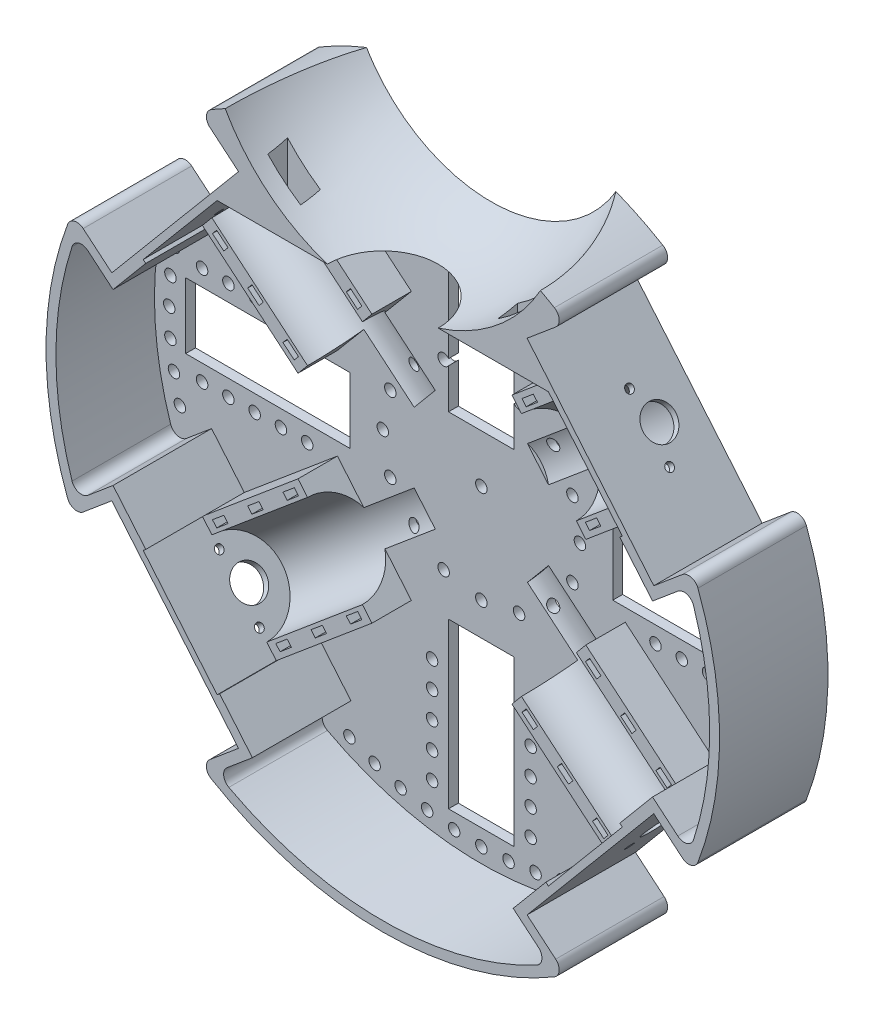
SolidWorks part; units mm, degrees
ref_plane "Front Plane" through (0, 0, 0) normal (0, 0, 1) x (1, 0, 0)
ref_plane "Top Plane" through (0, 0, 0) normal (0, 1, 0) x (1, 0, 0)
ref_plane "Right Plane" through (0, 0, 0) normal (1, 0, 0) x (0, 0, -1)
sketch "Sketch1" plane through (0, 0, 0) normal (0, 0, 1) x (1, 0, 0)
  circle A0 centre (0, 0) radius 102.5
  dimension "D1" = 205
extrude "Boss-Extrude1" add sketch "Sketch1" along normal blind 3
sketch "Sketch2" plane through (0, 0, 3) normal (0, 0, 1) x (1, 0, 0)
  line L0 (78.5196, 65.8857) -> (0, 0) construction
  line L1 (0, 0) -> (102.5, 0) construction
  line L2 (74.5568, 101.7228) -> (113.1241, 55.7601)
  line L3 (74.5568, 101.7228) -> (43.915, 76.0113)
  line L4 (113.1241, 55.7601) -> (82.4823, 30.0486)
  line L5 (43.915, 76.0113) -> (82.4823, 30.0486)
  line L6 (74.5568, 101.7228) -> (82.4823, 30.0486) construction
  line L7 (113.1241, 55.7601) -> (43.915, 76.0113) construction
  circle A0 centre (0, 0) radius 102.5 construction
  dimension "D1" = 40
  dimension "D2" = 60
  dimension "D3" = 40
extrude "Cut-Extrude1" cut sketch "Sketch2" against normal blind 3
sketch "Sketch3" plane through (0, 0, 3) normal (0, 0, 1) x (1, 0, 0)
  line L0 (51.9499, 66.4358) -> (74.4474, 39.6242)
  line L1 (51.9499, 66.4358) -> (21.3081, 40.7243)
  line L2 (74.4474, 39.6242) -> (43.8057, 13.9127)
  line L3 (21.3081, 40.7243) -> (43.8057, 13.9127)
  line L4 (43.915, 76.0113) -> (82.4823, 30.0486) construction
  point P6 (63.1987, 53.03)
  dimension "D1" = 35
  dimension "D2" = 40
extrude "Boss-Extrude2" add sketch "Sketch3" along normal blind 12
sketch "Sketch4" plane through (63.1987, 53.03, 0) normal (0.766, 0.6428, 0) x (0, 0, -1)
  line L0 (-15, -17.5) -> (-15, 17.5) construction
  circle A0 centre (-15, 0) radius 13
  dimension "D1" = 26
extrude "Cut-Extrude2" cut sketch "Sketch4" against normal blind 60
sketch "Sketch5" plane through (0, 0, 15) normal (0, 0, 1) x (1, 0, 0)
  line L0 (26.7453, 42.0231) -> (48.1945, 60.0211) construction
  line L1 (26.7453, 42.0231) -> (46.0289, 19.0417) construction
  line L2 (48.1945, 60.0211) -> (67.4782, 37.0398) construction
  line L3 (46.0289, 19.0417) -> (67.4782, 37.0398) construction
  line L4 (51.9499, 66.4358) -> (21.3081, 40.7243) construction
  line L5 (71.5549, 43.0714) -> (54.8424, 62.9886) construction
  line L6 (21.3081, 40.7243) -> (29.343, 31.1487) construction
  line L7 (57.8364, 48.5305) -> (63.1987, 53.03) construction
  line L8 (68.559, 39.2521) -> (65.1118, 36.3596)
  line L9 (68.559, 39.2521) -> (69.8446, 37.72)
  line L10 (65.1118, 36.3596) -> (66.3974, 34.8275)
  line L11 (69.8446, 37.72) -> (66.3974, 34.8275)
  line L12 (68.559, 39.2521) -> (66.3974, 34.8275) construction
  line L13 (65.1118, 36.3596) -> (69.8446, 37.72) construction
  line L14 (57.8344, 30.2531) -> (54.3872, 27.3605)
  line L15 (57.8344, 30.2531) -> (59.1199, 28.721)
  line L16 (54.3872, 27.3605) -> (55.6727, 25.8285)
  line L17 (59.1199, 28.721) -> (55.6727, 25.8285)
  line L18 (57.8344, 30.2531) -> (55.6727, 25.8285) construction
  line L19 (54.3872, 27.3605) -> (59.1199, 28.721) construction
  line L20 (43.6625, 18.3615) -> (47.1097, 21.2541)
  line L21 (43.6625, 18.3615) -> (44.9481, 16.8294)
  line L22 (47.1097, 21.2541) -> (48.3953, 19.722)
  line L23 (44.9481, 16.8294) -> (48.3953, 19.722)
  line L24 (43.6625, 18.3615) -> (48.3953, 19.722) construction
  line L25 (47.1097, 21.2541) -> (44.9481, 16.8294) construction
  line L26 (50.5609, 60.7014) -> (47.1137, 57.8088)
  line L27 (50.5609, 60.7014) -> (49.2754, 62.2334)
  line L28 (47.1137, 57.8088) -> (45.8282, 59.3409)
  line L29 (49.2754, 62.2334) -> (45.8282, 59.3409)
  line L30 (50.5609, 60.7014) -> (45.8282, 59.3409) construction
  line L31 (47.1137, 57.8088) -> (49.2754, 62.2334) construction
  line L32 (35.1035, 50.3419) -> (38.5507, 53.2344)
  line L33 (35.1035, 50.3419) -> (36.3891, 48.8098)
  line L34 (38.5507, 53.2344) -> (39.8363, 51.7023)
  line L35 (36.3891, 48.8098) -> (39.8363, 51.7023)
  line L36 (35.1035, 50.3419) -> (39.8363, 51.7023) construction
  line L37 (38.5507, 53.2344) -> (36.3891, 48.8098) construction
  line L38 (25.6645, 39.8108) -> (29.1117, 42.7033)
  line L39 (25.6645, 39.8108) -> (24.3789, 41.3429)
  line L40 (29.1117, 42.7033) -> (27.8261, 44.2354)
  line L41 (24.3789, 41.3429) -> (27.8261, 44.2354)
  line L42 (25.6645, 39.8108) -> (27.8261, 44.2354) construction
  line L43 (29.1117, 42.7033) -> (24.3789, 41.3429) construction
  point P13 (56.7535, 28.0408)
  point P14 (37.4699, 51.0221)
  dimension "D4" = 4.5
  dimension "D1" = 7
  dimension "D2" = 5
  dimension "D3" = 30
  dimension "D5" = 2
extrude "Cut-Extrude3" cut sketch "Sketch5" against normal through all
sketch "Sketch6" plane through (0, 0, 3) normal (0, 0, 1) x (1, 0, 0)
  line L0 (51.9499, 66.4358) -> (74.4474, 39.6242)
  line L1 (51.9499, 66.4358) -> (50.4178, 65.1502)
  line L2 (74.4474, 39.6242) -> (72.9154, 38.3386)
  line L3 (50.4178, 65.1502) -> (72.9154, 38.3386)
  dimension "D1" = 2
extrude "Boss-Extrude3" add sketch "Sketch6" along normal blind 30 and the other way blind 3
sketch "Sketch7" plane through (63.1987, 53.03, 0) normal (0.766, 0.6428, 0) x (0, 0, -1)
  line L0 (-15, 17.5) -> (-15, -17.5) construction
  line L1 (-33, 17.5) -> (-3, 17.5) construction
  line L2 (-33, -17.5) -> (-3, -17.5) construction
  line L3 (-15, 0) -> (-12, 0) construction
  line L4 (-3, 30) -> (-3, 17.5) construction
  circle A0 centre (-12, 0) radius 5
  circle A1 centre (-15, 9.5) radius 1.25
  circle A2 centre (-15, -9.5) radius 1.25
  dimension "D2" = 10
  dimension "D6" = 2.5
  dimension "D1" = 12
  dimension "D3" = 3
  dimension "D4" = 9.5
  dimension "D5" = 9.5
extrude "Cut-Extrude4" cut sketch "Sketch7" against normal blind 2
sketch "Sketch20" plane through (0, 0, 0) normal (0, 0, -1) x (-1, 0, 0)
  line L0 (-68.559, 39.2521) -> (-50.5609, 60.7014)
  line L1 (-68.559, 39.2521) -> (-65.1118, 36.3596)
  line L2 (-50.5609, 60.7014) -> (-47.1137, 57.8088)
  line L3 (-65.1118, 36.3596) -> (-47.1137, 57.8088)
  line L4 (-45.8282, 59.3409) -> (-47.1137, 57.8088) construction
  line L5 (-47.1137, 57.8088) -> (-50.5609, 60.7014) construction
  line L6 (-57.8344, 30.2531) -> (-39.8363, 51.7023)
  line L7 (-57.8344, 30.2531) -> (-54.3872, 27.3605)
  line L8 (-39.8363, 51.7023) -> (-36.3891, 48.8098)
  line L9 (-54.3872, 27.3605) -> (-36.3891, 48.8098)
  line L10 (-29.1117, 42.7033) -> (-47.1097, 21.2541)
  line L11 (-29.1117, 42.7033) -> (-25.6645, 39.8108)
  line L12 (-47.1097, 21.2541) -> (-43.6625, 18.3615)
  line L13 (-25.6645, 39.8108) -> (-43.6625, 18.3615)
  line L14 (-35.1035, 50.3419) -> (-36.3891, 48.8098) construction
  line L15 (-24.3789, 41.3429) -> (-25.6645, 39.8108) construction
extrude "Cut-Extrude13" cut sketch "Sketch20" against normal blind 1.5
mirror "Mirror1" about plane through (0, 0, 0) normal (1, 0, 0) of "Cut-Extrude13", "Cut-Extrude1", "Boss-Extrude2", "Cut-Extrude2", "Cut-Extrude3", "Boss-Extrude3", "Cut-Extrude4" second plane through (0, 0, 0) second plane normal (0, 1, 0)
chamfer "Chamfer2" distance 3 angle 45 24 edges at (56.1108, 28.8068, 1.5) (38.1127, 50.2561, 1.5) (27.3881, 41.257, 1.5) (45.3861, 19.8078, 1.5) (66.8354, 37.8058, 1.5) (48.8373, 59.2551, 1.5) (56.1108, -28.8068, 1.5) (38.1127, -50.2561, 1.5) (27.3881, -41.257, 1.5) (45.3861, -19.8078, 1.5) (66.8354, -37.8058, 1.5) (48.8373, -59.2551, 1.5) (-56.1108, 28.8068, 1.5) (-38.1127, 50.2561, 1.5) (-27.3881, 41.257, 1.5) (-45.3861, 19.8078, 1.5) (-66.8354, 37.8058, 1.5) (-48.8373, 59.2551, 1.5) (-56.1108, -28.8068, 1.5) (-38.1127, -50.2561, 1.5) (-27.3881, -41.257, 1.5) (-45.3861, -19.8078, 1.5) (-66.8354, -37.8058, 1.5) (-48.8373, -59.2551, 1.5)
sketch "Sketch8" plane through (0, 0, 3) normal (0, 0, 1) x (1, 0, 0)
  line L0 (74.4474, 39.6242) -> (82.4823, 30.0486) construction
  line L1 (82.4823, 30.0486) -> (94.3648, 40.0192) construction
  line L2 (82.4823, -30.0486) -> (94.3648, -40.0192) construction
  line L3 (74.4474, -39.6242) -> (82.4823, -30.0486) construction
  line L4 (43.915, -76.0113) -> (51.9499, -66.4358) construction
  line L5 (55.7975, -85.9819) -> (43.915, -76.0113) construction
  line L6 (-55.7975, -85.9819) -> (-43.915, -76.0113) construction
  line L7 (-43.915, -76.0113) -> (-51.9499, -66.4358) construction
  line L8 (-74.4474, 39.6242) -> (-82.4823, 30.0486) construction
  line L9 (-82.4823, 30.0486) -> (-94.3648, 40.0192) construction
  line L10 (-74.4474, -39.6242) -> (-82.4823, -30.0486) construction
  line L11 (-82.4823, -30.0486) -> (-94.3648, -40.0192) construction
  line L12 (74.4474, 39.6242) -> (82.4823, 30.0486)
  line L13 (82.4823, 30.0486) -> (94.3648, 40.0192)
  line L14 (82.4823, -30.0486) -> (94.3648, -40.0192)
  line L15 (74.4474, -39.6242) -> (82.4823, -30.0486)
  line L16 (43.915, -76.0113) -> (51.9499, -66.4358)
  line L17 (55.7975, -85.9819) -> (43.915, -76.0113)
  line L18 (-55.7975, -85.9819) -> (-43.915, -76.0113)
  line L19 (-43.915, -76.0113) -> (-51.9499, -66.4358)
  line L20 (-74.4474, 39.6242) -> (-82.4823, 30.0486)
  line L21 (-82.4823, 30.0486) -> (-94.3648, 40.0192)
  line L22 (-74.4474, -39.6242) -> (-82.4823, -30.0486)
  line L23 (-82.4823, -30.0486) -> (-94.3648, -40.0192)
  line L24 (72.1493, 37.6958) -> (82.1125, 25.8221)
  line L25 (82.1125, 25.8221) -> (93.1192, 35.0579)
  line L26 (82.1125, -25.8221) -> (93.1192, -35.0579)
  line L27 (72.1493, -37.6958) -> (82.1125, -25.8221)
  line L28 (-39.6885, -76.3811) -> (-49.6518, -64.5074)
  line L29 (-50.6953, -85.6168) -> (-39.6885, -76.3811)
  line L30 (50.6953, -85.6168) -> (39.6885, -76.3811)
  line L31 (39.6885, -76.3811) -> (49.6518, -64.5074)
  line L32 (-72.1493, 37.6958) -> (-82.1125, 25.8221)
  line L33 (-82.1125, 25.8221) -> (-93.1192, 35.0579)
  line L34 (-82.1125, -25.8221) -> (-93.1192, -35.0579)
  line L35 (-72.1493, -37.6958) -> (-82.1125, -25.8221)
  line L36 (-74.4474, 39.6242) -> (-72.1493, 37.6958)
  line L37 (-74.4474, -39.6242) -> (-72.1493, -37.6958)
  line L38 (-51.9499, -66.4358) -> (-49.6518, -64.5074)
  line L39 (49.6518, -64.5074) -> (51.9499, -66.4358)
  line L40 (72.1493, -37.6958) -> (74.4474, -39.6242)
  line L41 (72.1493, 37.6958) -> (74.4474, 39.6242)
  arc A0 (94.3648, -40.0192) -> (94.3648, 40.0192) centre (0, 0) ccw construction
  arc A1 (-55.7975, -85.9819) -> (55.7975, -85.9819) centre (0, 0) ccw construction
  arc A2 (-94.3648, 40.0192) -> (-94.3648, -40.0192) centre (0, 0) ccw construction
  arc A3 (94.3648, -40.0192) -> (94.3648, 40.0192) centre (0, 0) ccw
  arc A4 (-55.7975, -85.9819) -> (55.7975, -85.9819) centre (0, 0) ccw
  arc A5 (-94.3648, 40.0192) -> (-94.3648, -40.0192) centre (0, 0) ccw
  arc A6 (93.1192, -35.0579) -> (93.1192, 35.0579) centre (0, 0) ccw
  arc A7 (-50.6953, -85.6168) -> (50.6953, -85.6168) centre (0, 0) ccw
  arc A8 (-93.1192, 35.0579) -> (-93.1192, -35.0579) centre (0, 0) ccw
  dimension "D1" = 3
  dimension "D2" = 3
extrude "Boss-Extrude4" add sketch "Sketch8" along normal blind 30
sketch "Sketch9" plane through (0, 0, 3) normal (0, 0, 1) x (1, 0, 0)
  line L0 (43.915, 76.0113) -> (51.9499, 66.4358) construction
  line L1 (-43.915, 76.0113) -> (-51.9499, 66.4358) construction
  line L2 (55.7975, 85.9819) -> (43.915, 76.0113) construction
  line L3 (-55.7975, 85.9819) -> (-43.915, 76.0113) construction
  line L4 (43.915, 76.0113) -> (51.9499, 66.4358)
  line L5 (-43.915, 76.0113) -> (-51.9499, 66.4358)
  line L6 (55.7975, 85.9819) -> (43.915, 76.0113)
  line L7 (-55.7975, 85.9819) -> (-43.915, 76.0113)
  line L9 (-51.9499, 66.4358) -> (-50.4178, 65.1502)
  line L10 (-50.4178, 65.1502) -> (50.4178, 65.1502)
  line L11 (50.4178, 65.1502) -> (51.9499, 66.4358)
  arc A0 (55.7975, 85.9819) -> (-55.7975, 85.9819) centre (0, 0) ccw construction
  arc A1 (55.7975, 85.9819) -> (-55.7975, 85.9819) centre (0, 0) ccw
extrude "Boss-Extrude6" add sketch "Sketch9" along normal blind 30
sketch "Sketch10" plane through (0, 0, 33) normal (0, 0, 1) x (1, 0, 0)
  line L0 (-55, 117.5) -> (55, 117.5)
  line L1 (0, 117.5) -> (0, 102.5) construction
  arc A1 (-55, 117.5) -> (55, 117.5) centre (0, 117.5) ccw
  arc A2 (55.7975, 85.9819) -> (-55.7975, 85.9819) centre (0, 0) ccw construction
  dimension "D1" = 110
  dimension "D2" = 15
revolve "Cut-Revolve1" cut sketch "Sketch10" angle 360 about L0
fillet "Fillet1" radius 3 14 edges at (93.1192, 35.0579, 18) (93.1192, -35.0579, 18) (50.6953, -85.6168, 18) (-50.6953, -85.6168, 18) (55.7975, 85.9819, 16.5) (-93.1192, -35.0579, 18) (-93.1192, 35.0579, 18) (94.3648, 40.0192, 16.5) (55.7975, -85.9819, 16.5) (94.3648, -40.0192, 16.5) (-55.7975, 85.9819, 16.5) (-94.3648, 40.0192, 16.5) (-55.7975, -85.9819, 16.5) (-94.3648, -40.0192, 16.5)
sketch "Sketch13" plane through (0, 0, 3) normal (0, 0, 1) x (1, 0, 0)
  line L0 (-30, 0) -> (0, 0) construction
  circle A0 centre (-30, 0) radius 1.75
  circle A1 centre (-27.7164, 11.4805) radius 1.75
  circle A2 centre (-21.2132, 21.2132) radius 1.75
  circle A3 centre (-11.4805, 27.7164) radius 1.75
  circle A4 centre (0, 30) radius 1.75
  circle A5 centre (11.4805, 27.7164) radius 1.75
  circle A6 centre (21.2132, 21.2132) radius 1.75
  circle A7 centre (27.7164, 11.4805) radius 1.75
  circle A8 centre (30, 0) radius 1.75
  circle A9 centre (27.7164, -11.4805) radius 1.75
  circle A10 centre (21.2132, -21.2132) radius 1.75
  circle A11 centre (11.4805, -27.7164) radius 1.75
  circle A12 centre (0, -30) radius 1.75
  circle A13 centre (-11.4805, -27.7164) radius 1.75
  circle A14 centre (-21.2132, -21.2132) radius 1.75
  circle A15 centre (-27.7164, -11.4805) radius 1.75
  circle A16 centre (0, 0) radius 1.75
  point P37 (0, 0)
  dimension "D1" = 3.5
  dimension "D4" = 3.5
  dimension "D2" = 30
  dimension "D3" = 16
extrude "Cut-Extrude6" cut sketch "Sketch13" against normal through all both and the other way through all
sketch "Sketch14" plane through (0, 0, 3) normal (0, 0, 1) x (1, 0, 0)
  line L0 (-40, 10) -> (40, 10) construction
  line L1 (-90, 10) -> (-40, 10)
  line L2 (-90, 10) -> (-90, -10)
  line L3 (-90, -10) -> (-40, -10)
  line L4 (-40, 10) -> (-40, -10)
  line L5 (-90, 10) -> (-40, -10) construction
  line L6 (-90, -10) -> (-40, 10) construction
  line L7 (40, 10) -> (90, 10)
  line L8 (40, 10) -> (40, -10)
  line L9 (40, -10) -> (90, -10)
  line L10 (90, 10) -> (90, -10)
  line L11 (40, 10) -> (90, -10) construction
  line L12 (40, -10) -> (90, 10) construction
  line L13 (-10, -90) -> (10, -90)
  line L14 (-10, -90) -> (-10, -40)
  line L15 (-10, -40) -> (10, -40)
  line L16 (10, -90) -> (10, -40)
  line L17 (-10, -90) -> (10, -40) construction
  line L18 (-10, -40) -> (10, -90) construction
  line L19 (40, -10) -> (-40, -10) construction
  line L20 (-40, 0) -> (40, 0) construction
  line L21 (0, 0) -> (0, -40) construction
  point P0 (-65, 0)
  point P5 (65, 0)
  point P10 (0, -65)
  dimension "D1" = 40
  dimension "D2" = 40
  dimension "D3" = 50
  dimension "D4" = 20
extrude "Cut-Extrude7" cut sketch "Sketch14" against normal through all and the other way through all
sketch "Sketch15" plane through (0, 0, 3) normal (0, 0, 1) x (1, 0, 0)
  line L0 (-95, 0) -> (0, 0) construction
  circle A0 centre (-95, 0) radius 1.75
  dimension "D1" = 3.5
  dimension "D2" = 95
extrude "Cut-Extrude8" cut sketch "Sketch15" against normal through all
pattern_circular "CirPattern1" count 4 every 5 about axis through (0, 0, 0) along (0, 0, 1) of "Cut-Extrude8"
mirror "Mirror2" about plane through (0, 0, 0) normal (1, 0, 0) of "CirPattern1", "Cut-Extrude8"
sketch "Sketch16" plane through (0, 0, 3) normal (0, 0, 1) x (1, 0, 0)
  line L0 (0, 0) -> (0, -95) construction
  circle A0 centre (0, -95) radius 1.75
  dimension "D1" = 3.5
  dimension "D2" = 95
extrude "Cut-Extrude9" cut sketch "Sketch16" against normal through all
pattern_circular "CirPattern2" count 6 every 5 about axis through (0, 0, 0) along (0, 0, 1) of "Cut-Extrude9"
sketch "Sketch17" plane through (0, 0, 3) normal (0, 0, 1) x (1, 0, 0)
  line L0 (0, 14.6502) -> (0, 0) construction
  line L1 (-10, 64.6502) -> (10, 64.6502)
  line L2 (-10, 64.6502) -> (-10, 14.6502)
  line L3 (-10, 14.6502) -> (10, 14.6502)
  line L4 (10, 64.6502) -> (10, 14.6502)
  line L5 (-10, 64.6502) -> (10, 14.6502) construction
  line L6 (-10, 14.6502) -> (10, 64.6502) construction
  line L7 (-50.4178, 65.1502) -> (50.4178, 65.1502) construction
  point P0 (0, 39.6502)
  dimension "D1" = 50
  dimension "D2" = 20
  dimension "D3" = 0.5
extrude "Cut-Extrude10" cut sketch "Sketch17" against normal through all
sketch "Sketch18" plane through (0, 0, 3) normal (0, 0, 1) x (1, 0, 0)
  line L0 (-85, 15) -> (-85, -15) construction
  line L1 (-90, 0) -> (-85, 0) construction
  line L2 (-90, 10) -> (-90, -10) construction
  circle A0 centre (-85, 15) radius 1.75
  circle A1 centre (-85, -15) radius 1.75
  dimension "D3" = 3.5
  dimension "D1" = 5
  dimension "D2" = 30
extrude "Cut-Extrude11" cut sketch "Sketch18" against normal through all and the other way through all
pattern_linear "LPattern1" count 5 spacing 8 along (1, 0, 0) of "Cut-Extrude11"
pattern_circular "CirPattern3" count 3 every 90 about axis through (0, 0, 3) along (0, 0, -1) of "LPattern1", "Cut-Extrude11"
sketch "Sketch21" plane through (0, 65.1502, 0) normal (0, -1, 0) x (1, 0, 0)
  line L0 (-35, 25) -> (35, 25) construction
  line L1 (0, 0) -> (0, 25) construction
  line L3 (-40, 28) -> (-30, 28)
  line L4 (-40, 28) -> (-40, 22)
  line L5 (-40, 22) -> (-30, 22)
  line L6 (-30, 28) -> (-30, 22)
  line L7 (-40, 28) -> (-30, 22) construction
  line L8 (-40, 22) -> (-30, 28) construction
  line L9 (30, 28) -> (40, 28)
  line L10 (30, 28) -> (30, 22)
  line L11 (30, 22) -> (40, 22)
  line L12 (40, 28) -> (40, 22)
  line L13 (30, 28) -> (40, 22) construction
  line L14 (30, 22) -> (40, 28) construction
  point P13 (-30, 28.4606)
  dimension "D1" = 25
  dimension "D2" = 10
  dimension "D3" = 70
  dimension "D4" = 6
extrude "Cut-Extrude14" cut sketch "Sketch21" against normal through all
